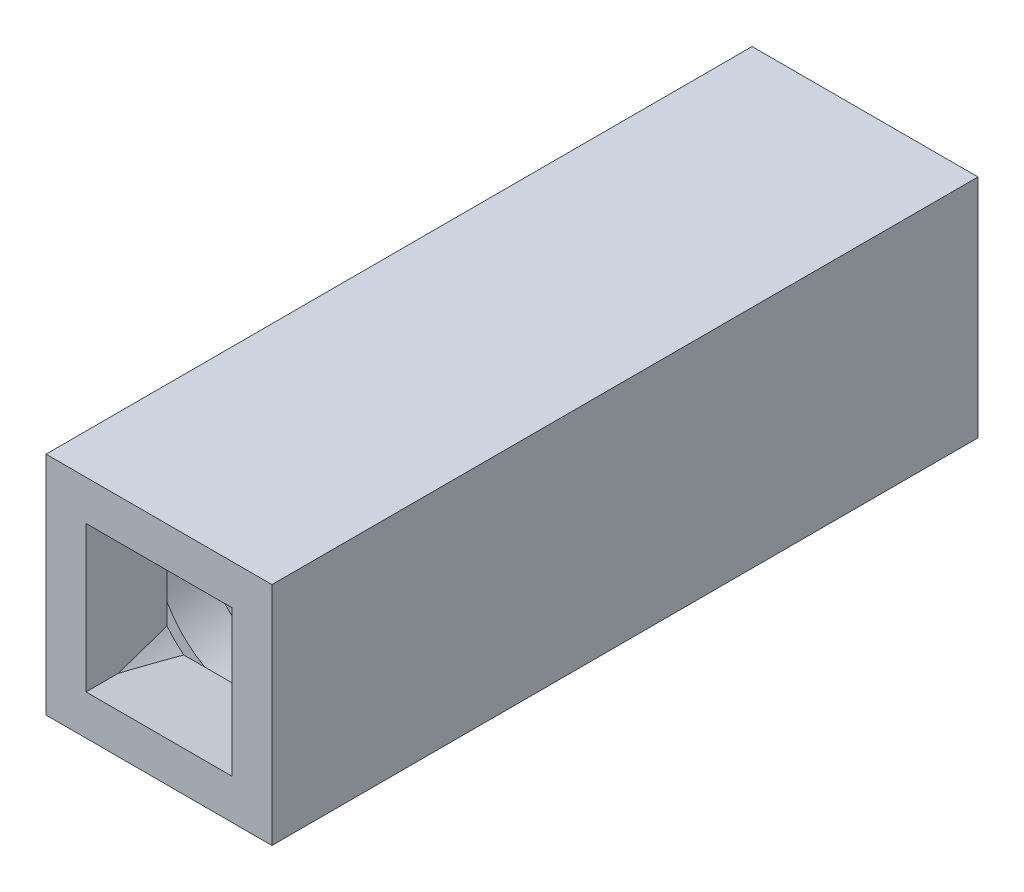
SolidWorks part; units mm, degrees
ref_plane "Front Plane" through (0, 0, 0) normal (0, 0, 1) x (1, 0, 0)
ref_plane "Top Plane" through (0, 0, 0) normal (0, 1, 0) x (1, 0, 0)
ref_plane "Right Plane" through (0, 0, 0) normal (1, 0, 0) x (0, 0, -1)
sketch "Sketch1" plane through (0, 0, 0) normal (0, 0, 1) x (1, 0, 0)
  circle A0 centre (0, 0) radius 26.67
  circle A1 centre (0, 0) radius 29.845
  dimension "D1" = 53.34
  dimension "D2" = 3.175
extrude "Boss-Extrude1" add sketch "Sketch1" along normal blind 165.1
sketch "Sketch2" plane through (0, 0, 0) normal (0, 1, 0) x (1, 0, 0)
  line L1 (-29.845, 0.8555) -> (29.845, 0.8555)
  line L2 (-29.845, 0.8555) -> (-29.845, -37.2445)
  line L3 (-29.845, -37.2445) -> (29.845, -37.2445)
  line L4 (29.845, 0.8555) -> (29.845, -37.2445)
  point P4 (0, 0.8555)
  dimension "D1" = 59.69
  dimension "D2" = 38.1
extrude "Cut-Extrude1" cut sketch "Sketch2" against normal through all
sketch "Sketch3" plane through (0, 0, 0) normal (0, 0, -1) x (-1, 0, 0)
  line L0 (-29.845, 0) -> (-6.985, 0)
  line L1 (6.985, 0) -> (29.845, 0)
  arc A0 (29.845, 0) -> (-29.845, 0) centre (0, 0) ccw construction
  arc A1 (29.845, 0) -> (-29.845, 0) centre (0, 0) ccw
  arc A2 (6.985, 0) -> (-6.985, 0) centre (0, 0) ccw
  dimension "D1" = 6.985
extrude "Boss-Extrude2" add sketch "Sketch3" against normal blind 6.35
sketch "Sketch4" plane through (0, 0, 165.1) normal (0, 0, 1) x (1, 0, 0)
  line L0 (0, 0) -> (0, 26.67) construction
  line L1 (1.27, 26.6397) -> (1.27, 9.45)
  line L3 (9.5173, 1.27) -> (26.6397, 1.27)
  line L4 (29.818, 1.27) -> (30.6047, 1.27)
  line L5 (0, 0) -> (26.67, 0) construction
  line L7 (9.489, -1.4654) -> (26.6397, -1.27)
  line L8 (1.27, -26.6397) -> (1.4535, -9.4251)
  line L9 (-9.3342, 1.4654) -> (-26.6397, 1.27)
  line L10 (-1.27, 26.6397) -> (-1.4773, 9.3973)
  line L11 (-1.27, -26.6397) -> (-1.4773, -9.3973)
  line L12 (-9.3342, -1.4654) -> (-26.6397, -1.27)
  arc A0 (26.67, 0) -> (-26.67, 0) centre (0, 0) ccw construction
  circle A1 centre (0, 0) radius 29.845 construction
  circle A2 centre (0, 0) radius 29.845
  arc A3 (26.6397, 1.27) -> (1.27, 26.6397) centre (0, 0) ccw
  arc A4 (26.6397, -1.27) -> (1.27, -26.6397) centre (0, 0) cw
  arc A5 (-26.6397, 1.27) -> (-1.27, 26.6397) centre (0, 0) cw
  arc A6 (-26.6397, -1.27) -> (-1.27, -26.6397) centre (0, 0) ccw
  circle A7 centre (0, 0) radius 6.985
  arc A8 (-1.4773, 9.3973) -> (-9.3342, 1.4654) centre (0.0774, 0) ccw
  arc A9 (9.5173, 1.27) -> (1.27, 9.45) centre (0.0774, 0) ccw
  arc A10 (1.4535, -9.4251) -> (9.489, -1.4654) centre (0.0774, 0) ccw
  arc A11 (-9.3342, -1.4654) -> (-1.4773, -9.3973) centre (0.0774, 0) ccw
  circle M7 centre (0, 0) radius 29.845
  circle M8 centre (0, 0) radius 26.67
  dimension "D3" = 13.97
  dimension "D2" = 19.05
  dimension "D1" = 2.54
  dimension "D4" = 2.54
sketch "Sketch5" plane through (0, 0, 0) normal (0, 0, -1) x (-1, 0, 0)
  line L0 (-29.818, 1.27) -> (-30.6047, 1.27) construction
  line L1 (-29.818, 1.27) -> (-30.6047, 1.27)
  line L2 (26.6397, -1.27) -> (9.3342, -1.4654)
  line L3 (1.4773, -9.3973) -> (1.27, -26.6397)
  line L4 (26.6397, -1.27) -> (9.3342, -1.4654)
  line L5 (1.4773, -9.3973) -> (1.27, -26.6397)
  line L6 (9.3342, 1.4654) -> (26.6397, 1.27)
  line L7 (1.27, 26.6397) -> (1.4773, 9.3973)
  line L8 (9.3342, 1.4654) -> (26.6397, 1.27)
  line L9 (1.27, 26.6397) -> (1.4773, 9.3973)
  line L10 (-9.489, -1.4654) -> (-26.6397, -1.27)
  line L11 (-1.27, -26.6397) -> (-1.4535, -9.4251)
  line L12 (-9.489, -1.4654) -> (-26.6397, -1.27)
  line L13 (-1.27, -26.6397) -> (-1.4535, -9.4251)
  line L14 (-1.27, 9.45) -> (-1.27, 26.6397)
  line L15 (-26.6397, 1.27) -> (-9.5173, 1.27)
  line L16 (-1.27, 9.45) -> (-1.27, 26.6397)
  line L17 (-26.6397, 1.27) -> (-9.5173, 1.27)
  circle A1 centre (0, 0) radius 6.985
  circle A2 centre (0, 0) radius 6.985
  circle A3 centre (0, 0) radius 29.845
  circle A4 centre (0, 0) radius 29.845
  arc A6 (1.27, -26.6397) -> (26.6397, -1.27) centre (0, 0) ccw
  arc A7 (1.4773, -9.3973) -> (9.3342, -1.4654) centre (-0.0774, 0) ccw
  arc A8 (1.27, -26.6397) -> (26.6397, -1.27) centre (0, 0) ccw
  arc A9 (1.4773, -9.3973) -> (9.3342, -1.4654) centre (-0.0774, 0) ccw
  arc A10 (26.6397, 1.27) -> (1.27, 26.6397) centre (0, 0) ccw
  arc A11 (9.3342, 1.4654) -> (1.4773, 9.3973) centre (-0.0774, 0) ccw
  arc A12 (26.6397, 1.27) -> (1.27, 26.6397) centre (0, 0) ccw
  arc A13 (9.3342, 1.4654) -> (1.4773, 9.3973) centre (-0.0774, 0) ccw
  arc A14 (-26.6397, -1.27) -> (-1.27, -26.6397) centre (0, 0) ccw
  arc A15 (-9.489, -1.4654) -> (-1.4535, -9.4251) centre (-0.0774, 0) ccw
  arc A16 (-26.6397, -1.27) -> (-1.27, -26.6397) centre (0, 0) ccw
  arc A17 (-9.489, -1.4654) -> (-1.4535, -9.4251) centre (-0.0774, 0) ccw
  arc A18 (-1.27, 26.6397) -> (-26.6397, 1.27) centre (0, 0) ccw
  arc A19 (-1.27, 9.45) -> (-9.5173, 1.27) centre (-0.0774, 0) ccw
  arc A20 (-1.27, 26.6397) -> (-26.6397, 1.27) centre (0, 0) ccw
  arc A21 (-1.27, 9.45) -> (-9.5173, 1.27) centre (-0.0774, 0) ccw
  arc M19 (29.845, 0) -> (-29.845, 0) centre (0, 0) ccw
  line M20 (-29.845, 0) -> (-6.985, 0)
  arc M21 (-6.985, 0) -> (6.985, 0) centre (0, 0) cw
  line M22 (6.985, 0) -> (29.845, 0)
  dimension "D1" = 0
  dimension "D2" = 0
  dimension "D3" = 0
  dimension "D4" = 0
  dimension "D5" = 0
  dimension "D6" = 0
extrude "Boss-Extrude4" add sketch "Sketch5" against normal blind 6.35 contours A20 L16 L9 A12 L8 L17 M21 M22 M19 M20 | L16 A21 L17 A4 L8 A13 L9 A2 L5 A9 L4 A8 L12 A17 L13 A16 M21 M20 M22 | A17 L12 A16 L13 | A9 L5 A8 L4 | A13 L8 A12 L9 | A21 L16 A20 L17 region at (-12.7089, -12.7031, 0) region at (-12.7089, 12.7031, 0) region at (12.719, -12.7249, 0) region at (12.6879, 12.6906, 0) region at (0.0199, -14.2557, 0) region at (-0.0428, 14.3018, 0)
extrude "Boss-Extrude5" add sketch "Sketch4" against normal blind 6.35 contours M7 M8 | L12 A11 L11 L8 A10 L7 L3 A9 L1 L10 A8 L9 A7 M8 region at (0.5157, 18.0449, 165.1) region at (-28.9943, -0.6172, 165.1)
sketch "Sketch6" plane through (0, 0, 0) normal (0, 0, 1) x (1, 0, 0)
  line L1 (30.48, -30.48) -> (-30.48, -30.48)
  line L2 (30.48, -30.48) -> (30.48, 30.48)
  line L3 (30.48, 30.48) -> (-30.48, 30.48)
  line L4 (-30.48, -30.48) -> (-30.48, 30.48)
  line L5 (30.48, -30.48) -> (-30.48, 30.48) construction
  line L6 (30.48, 30.48) -> (-30.48, -30.48) construction
  circle A1 centre (0, 0) radius 29.845
  point P0 (0, 0)
extrude "Boss-Extrude7" add sketch "Sketch6" along normal blind 190.5
sketch "Sketch7" plane through (0, 0, 190.5) normal (0, 0, 1) x (1, 0, 0)
  line L1 (-19.685, -19.685) -> (19.685, -19.685)
  line L2 (-19.685, -19.685) -> (-19.685, 19.685)
  line L3 (-19.685, 19.685) -> (19.685, 19.685)
  line L4 (19.685, -19.685) -> (19.685, 19.685)
  line L5 (-19.685, -19.685) -> (19.685, 19.685) construction
  line L6 (-19.685, 19.685) -> (19.685, -19.685) construction
  point P0 (0, 0)
  line M5 (-30.48, 30.48) -> (-30.48, -30.48)
  line M6 (-30.48, -30.48) -> (30.48, -30.48)
  line M7 (30.48, -30.48) -> (30.48, 30.48)
  line M8 (30.48, 30.48) -> (-30.48, 30.48)
  circle M9 centre (0, 0) radius 29.845
  dimension "D1" = 39.37
  dimension "D2" = 39.37
extrude "Boss-Extrude8" add sketch "Sketch7" against normal blind 25.4 draft 8 contours M8 M5 M6 M7 M9 | L4 L1 L2 L3 M9 region at (0, 30.3938, 190.5) region at (-29.0009, 0, 190.5)
